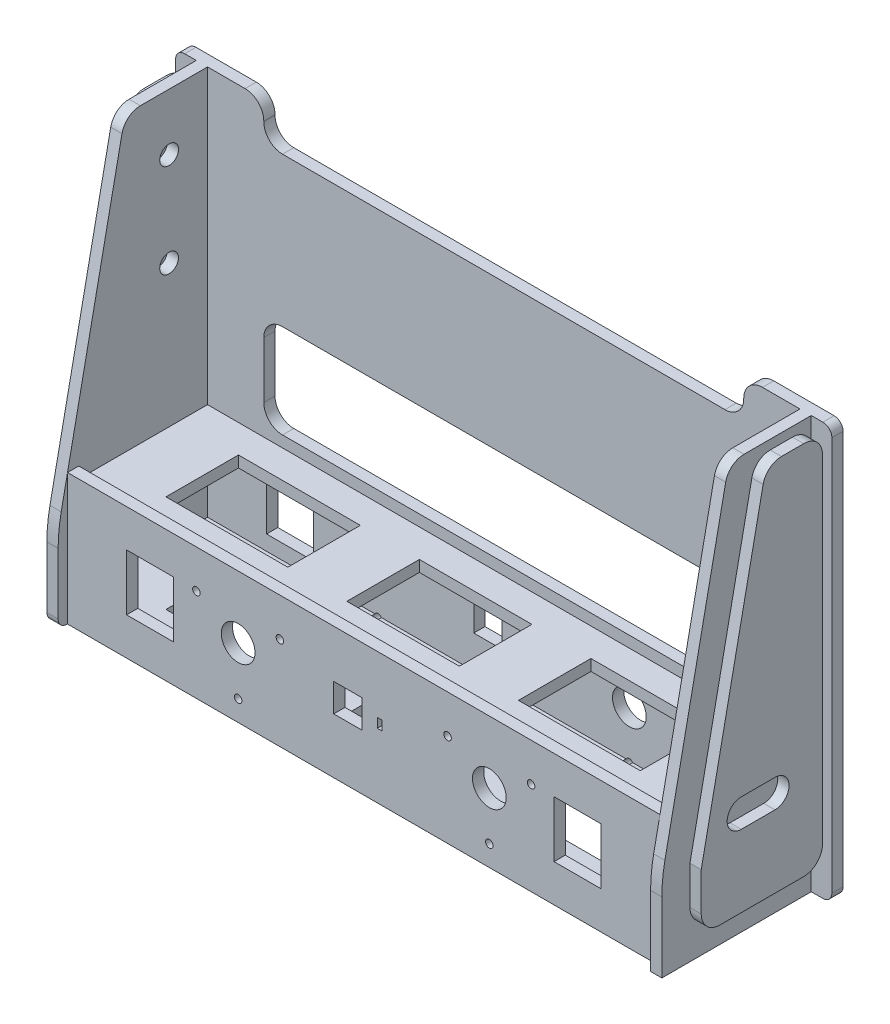
SolidWorks part; units mm, degrees
material "Birch plywood FK"
ref_plane "Спереди" through (0, 0, 0) normal (0, 0, 1) x (1, 0, 0)
ref_plane "Сверху" through (0, 0, 0) normal (0, 1, 0) x (1, 0, 0)
ref_plane "Справа" through (0, 0, 0) normal (1, 0, 0) x (0, 0, -1)
sketch "Эскиз1" plane through (0, 0, 0) normal (1, 0, 0) x (0, 0, -1)
  line L0 (0, 220) -> (0, 0)
  line L1 (0, 0) -> (-95, 0)
  line L2 (-95, 0) -> (-50, 220)
  line L3 (-50, 220) -> (0, 220)
  dimension "D1" = 220
  dimension "D2" = 95
  dimension "D3" = 50
extrude "Бобышка-Вытянуть1" add sketch "Эскиз1" along normal blind 340
sketch "Эскиз2" plane through (0, 220, 0) normal (0, 1, 0) x (1, 0, 0)
  line L0 (170, -95) -> (170, 0) construction
  line L1 (340, -95) -> (0, -95) construction
  line L2 (340, 0) -> (0, 0) construction
  line L3 (340, -50) -> (340, -95) construction
  line L4 (12, -95) -> (328, -95)
  line L5 (12, -95) -> (12, -6)
  line L6 (12, -6) -> (328, -6)
  line L7 (328, -95) -> (328, -6)
  line L8 (12, -95) -> (328, -6) construction
  line L9 (12, -6) -> (328, -95) construction
  point P6 (170, -50.5)
  dimension "D1" = 12
  dimension "D2" = 6
extrude "Вырез-Вытянуть1" cut sketch "Эскиз2" against normal offset from surface (150 mm away) 70 up to face at (170, 0, 47.5)
sketch "Эскиз3" plane through (0, 70, 0) normal (0, 1, 0) x (1, 0, 0)
  line L0 (340, -95) -> (0, -95) construction
  line L1 (12, -80.6818) -> (328, -80.6818)
  line L2 (12, -80.6818) -> (12, -95)
  line L3 (12, -95) -> (328, -95)
  line L4 (328, -80.6818) -> (328, -95)
extrude "Вырез-Вытянуть2" cut sketch "Эскиз3" against normal through all
sketch "Эскиз4" plane through (0, 0, 80.6818) normal (0, 0, 1) x (1, 0, 0)
  line L0 (170, 70) -> (170, 0) construction
  line L1 (12, 70) -> (328, 70) construction
  line L2 (328, 0) -> (12, 0) construction
  line L3 (12, 0) -> (12, 70) construction
  line L4 (328, 12) -> (12, 12)
  line L5 (328, 12) -> (328, 58)
  line L6 (328, 58) -> (12, 58)
  line L7 (12, 12) -> (12, 58)
  line L8 (328, 12) -> (12, 58) construction
  line L9 (328, 58) -> (12, 12) construction
  line L10 (12, 70) -> (328, 70) construction
  line L12 (328, 64) -> (12, 64)
  line L13 (328, 64) -> (328, 70)
  line L14 (328, 70) -> (12, 70)
  line L15 (12, 64) -> (12, 70)
  line L16 (328, 64) -> (12, 70) construction
  line L17 (328, 70) -> (12, 64) construction
  line L18 (328, 6) -> (12, 6)
  line L19 (328, 6) -> (328, 0)
  line L20 (328, 0) -> (12, 0)
  line L21 (12, 6) -> (12, 0)
  line L22 (328, 6) -> (12, 0) construction
  line L23 (328, 0) -> (12, 6) construction
  point P6 (170, 35)
  point P15 (170, 67)
  point P21 (170, 3)
  dimension "D1" = 12
  dimension "D2" = 6
extrude "Вырез-Вытянуть3" cut sketch "Эскиз4" against normal offset from surface (68.6818 mm away) 6 from offset 6 up to face at (170, 110, 0) offset against normal yes
sketch "Эскиз5" plane through (0, 0, 6) normal (0, 0, 1) x (1, 0, 0)
  line L0 (170, 220) -> (170, 70) construction
  line L1 (328, 220) -> (12, 220) construction
  line L2 (12, 70) -> (328, 70) construction
  line L3 (12, 64) -> (12, 220) construction
  line L4 (298, 70) -> (42, 70)
  line L5 (298, 70) -> (298, 120)
  line L6 (298, 120) -> (42, 120)
  line L7 (42, 70) -> (42, 120)
  line L8 (298, 70) -> (42, 120) construction
  line L9 (298, 120) -> (42, 70) construction
  point P6 (170, 95)
  dimension "D1" = 30
  dimension "D2" = 50
extrude "Вырез-Вытянуть4" cut sketch "Эскиз5" against normal through all
sketch "Эскиз6" plane through (0, 70, 0) normal (0, 1, 0) x (1, 0, 0)
  line L0 (170, 0) -> (170, -80.6818) construction
  line L1 (42, 0) -> (298, 0) construction
  line L2 (12, -80.6818) -> (328, -80.6818) construction
  line L3 (12, -6) -> (42, -6) construction
  line L4 (140, -40.3409) -> (12, -40.3409) construction
  line L5 (12, -6) -> (12, -74.6818) construction
  line L6 (200, -59.6818) -> (140, -59.6818)
  line L7 (200, -59.6818) -> (200, -21)
  line L8 (200, -21) -> (140, -21)
  line L9 (140, -59.6818) -> (140, -21)
  line L10 (200, -59.6818) -> (140, -21) construction
  line L11 (200, -21) -> (140, -59.6818) construction
  line L13 (108.5, -21) -> (43.5, -21)
  line L14 (328, -6) -> (328, -74.6818) construction
  line L15 (328, -40.3409) -> (200, -40.3409) construction
  line L16 (108.5, -21) -> (108.5, -59.6818)
  line L17 (108.5, -59.6818) -> (43.5, -59.6818)
  line L19 (43.5, -21) -> (43.5, -59.6818)
  line L20 (108.5, -21) -> (43.5, -59.6818) construction
  line L21 (108.5, -59.6818) -> (43.5, -21) construction
  line L22 (296.5, -21) -> (231.5, -21)
  line L23 (296.5, -21) -> (296.5, -59.6818)
  line L24 (296.5, -59.6818) -> (231.5, -59.6818)
  line L25 (231.5, -21) -> (231.5, -59.6818)
  line L26 (296.5, -21) -> (231.5, -59.6818) construction
  line L27 (296.5, -59.6818) -> (231.5, -21) construction
  point P6 (170, -40.3409)
  point P18 (76, -40.3409)
  point P28 (264, -40.3409)
  dimension "D1" = 15
  dimension "D2" = 60
  dimension "D3" = 65
extrude "Вырез-Вытянуть5" cut sketch "Эскиз6" against normal through all
sketch "Эскиз8" plane through (0, 0, 0) normal (-1, 0, 0) x (0, 0, 1)
  line L0 (95, 0) -> (0, 0) construction
  line L1 (85.6818, 70) -> (95, 70)
  line L2 (85.6818, 70) -> (85.6818, 0)
  line L3 (85.6818, 0) -> (95, 0)
  line L4 (95, 70) -> (95, 0)
  line L5 (80.6818, 0) -> (80.6818, 70) construction
  line L6 (80.6818, 70) -> (74.6818, 70) construction
  dimension "D1" = 5
extrude "Вырез-Вытянуть7" cut sketch "Эскиз8" against normal through all
sketch "Эскиз10" plane through (0, 220, 0) normal (0, 1, 0) x (1, 0, 0)
  line L0 (328, -6) -> (12, -6) construction
  line L1 (0, 0) -> (-5, 0)
  line L2 (0, 0) -> (0, -6)
  line L3 (0, -6) -> (-5, -6)
  line L4 (-5, 0) -> (-5, -6)
  line L5 (340, 0) -> (345, 0)
  line L6 (340, 0) -> (340, -6)
  line L7 (340, -6) -> (345, -6)
  line L8 (345, 0) -> (345, -6)
  dimension "D1" = 5
  dimension "D2" = 5
extrude "Бобышка-Вытянуть3" add sketch "Эскиз10" against normal up to surface (220 mm away) up to face at (170, 0, 63.0114)
sketch "Эскиз12" plane through (0, 0, 0) normal (-1, 0, 0) x (0, 0, 1)
  circle A0 centre (26.5, 189.7) radius 5
  circle A1 centre (26.5, 139.7) radius 5
  dimension "D1" = 10
extrude "Вырез-Вытянуть9" cut sketch "Эскиз12" against normal offset from surface (328 mm away) 6 from offset 6 up to face at (340, 75.1111, 50.2409) offset against normal yes
sketch "Эскиз13" plane through (0, 0, 6) normal (0, 0, 1) x (1, 0, 0)
  line L0 (334, 184.7) -> (345, 184.7) construction
  line L1 (345, 0) -> (345, 220) construction
  line L2 (306.85, 184.7) -> (306.85, 144.7) construction
  line L3 (334, 144.7) -> (345, 144.7) construction
  line L4 (306.85, 164.7) -> (345, 164.7) construction
  circle A0 centre (306.85, 164.7) radius 16.4
  circle A2 centre (291.35, 180.2) radius 1.5
  circle A3 centre (322.35, 180.2) radius 1.5
  circle A4 centre (322.35, 149.2) radius 1.5
  circle A5 centre (291.35, 149.2) radius 1.5
  circle A6 centre (306.85, 164.7) radius 16.4 construction
  point P0 (306.85, 164.7)
  dimension "D1" = 3
extrude "Вырез-Вытянуть10" cut sketch "Эскиз13" against normal through all
fillet "Скругление2" radius 10 2 edges at (6, 220, 50) (334, 220, 50)
fillet "Скругление4" radius 80 2 edges at (334, 45.5556, 85.6818) (6, 45.5556, 85.6818)
sketch "Эскиз16" plane through (0, 0, 80.6818) normal (0, 0, 1) x (1, 0, 0)
  circle A0 centre (103, 36.7238) radius 9
  circle A1 centre (237, 36.7238) radius 9
  dimension "D1" = 18
extrude "Вырез-Вытянуть12" cut sketch "Эскиз16" against normal through all
sketch "Эскиз19" plane through (0, 0, 80.6818) normal (0, 0, 1) x (1, 0, 0)
  line L0 (161.5, 37) -> (178.5, 37) construction
  line L1 (169, 29.5) -> (154, 29.5)
  line L2 (169, 29.5) -> (169, 44.5)
  line L3 (169, 44.5) -> (154, 44.5)
  line L4 (154, 29.5) -> (154, 44.5)
  line L5 (169, 29.5) -> (154, 44.5) construction
  line L6 (169, 44.5) -> (154, 29.5) construction
  line L7 (179.75, 34.5) -> (177.25, 34.5)
  line L8 (179.75, 34.5) -> (179.75, 39.5)
  line L9 (179.75, 39.5) -> (177.25, 39.5)
  line L10 (177.25, 34.5) -> (177.25, 39.5)
  line L11 (179.75, 34.5) -> (177.25, 39.5) construction
  line L12 (179.75, 39.5) -> (177.25, 34.5) construction
  line L13 (170, 37) -> (170, -29) construction
  line L14 (153.0926, -29) -> (186.9074, -29) construction
  line L15 (60, 24.5) -> (280, 24.5) construction
  circle A0 centre (125.2775, 49.5857) radius 2
  circle A1 centre (80.7225, 49.5857) radius 2
  circle A2 centre (103, 11) radius 2
  circle A3 centre (214.7225, 49.5857) radius 2
  circle A4 centre (259.2775, 49.5857) radius 2
  circle A5 centre (237, 11) radius 2
  point P0 (161.5, 37)
  point P5 (178.5, 37)
  dimension "D7" = 4
  dimension "D1" = 5
  dimension "D2" = 2.5
  dimension "D3" = 12.5
  dimension "D4" = 17
  dimension "D5" = 15
  dimension "D6" = 15
extrude "Вырез-Вытянуть15" cut sketch "Эскиз19" against normal through all
fillet "Скругление5" radius 4.8 5 edges at (-5, 220, 3) (6, 0, 85.6818) (-5, 0, 3) (345, 0, 3) (345, 220, 3)
fillet "Скругление6" radius 10 4 edges at (298, 70, 3) (298, 120, 3) (42, 70, 3) (42, 120, 3)
sketch "Эскиз20" plane through (0, 0, 6) normal (0, 0, 1) x (1, 0, 0)
  line L0 (319.5142, 124.6) -> (309.5142, 124.6) construction
  line L1 (319.5142, 124.1) -> (309.5142, 124.1)
  line L2 (319.5142, 125.1) -> (309.5142, 125.1)
  line L3 (319.5142, 115.1) -> (309.5142, 115.1) construction
  line L4 (319.5142, 114.6) -> (309.5142, 114.6)
  line L5 (319.5142, 115.6) -> (309.5142, 115.6)
  arc A0 (319.5142, 124.1) -> (319.5142, 125.1) centre (319.5142, 124.6) ccw
  arc A1 (309.5142, 125.1) -> (309.5142, 124.1) centre (309.5142, 124.6) ccw
  arc A2 (319.5142, 114.6) -> (319.5142, 115.6) centre (319.5142, 115.1) ccw
  arc A3 (309.5142, 115.6) -> (309.5142, 114.6) centre (309.5142, 115.1) ccw
  point P2 (314.5142, 124.6)
  point P7 (314.5142, 115.1)
  dimension "D1" = 1
  dimension "D2" = 10
extrude "Вырез-Вытянуть16" cut sketch "Эскиз20" against normal through all
sketch "Эскиз21" plane through (0, 0, 6) normal (0, 0, 1) x (1, 0, 0)
  line L0 (170, 220) -> (170, 0) construction
  line L1 (328, 220) -> (12, 220) construction
  line L2 (328, 0) -> (12, 0) construction
  line L3 (12, 70) -> (12, 212.004) construction
  line L4 (298, 199.7) -> (42, 199.7)
  line L5 (298, 199.7) -> (298, 220)
  line L6 (298, 220) -> (42, 220)
  line L7 (42, 199.7) -> (42, 220)
  line L8 (298, 199.7) -> (42, 220) construction
  line L9 (298, 220) -> (42, 199.7) construction
  line L10 (156.6778, 202.7) -> (190.4925, 202.7) construction
  point P6 (170, 209.85)
  dimension "D1" = 30
  dimension "D2" = 3
extrude "Вырез-Вытянуть17" cut sketch "Эскиз21" against normal through all
fillet "Скругление7" radius 10 4 edges at (298, 199.7, 3) (298, 220, 3) (42, 199.7, 3) (42, 220, 3)
ref_plane "Плоскость1" through (170, 0, 0) normal (-1, 0, 0) x (0, 0, 1)
sketch "Эскиз22" plane through (0, 0, 0) normal (-1, 0, 0) x (0, 0, 1)
  line L0 (16, 215) -> (27.8611, 215)
  line L2 (37.6583, 207.004) -> (70.6818, 45.5556)
  line L3 (70.6818, 45.5556) -> (70.6818, 25)
  line L4 (60.6818, 15) -> (16, 15)
  line L5 (6, 220) -> (41.8384, 220) construction
  line L6 (51.6356, 212.004) -> (84.059, 53.4893) construction
  line L7 (80.8818, 0) -> (6, 0) construction
  line L8 (85.6818, 37.4576) -> (85.6818, 4.8) construction
  line L9 (6, 0) -> (6, 220) construction
  line L10 (6, 205) -> (6, 220)
  line L11 (6, 220) -> (50, 220)
  line L12 (50, 220) -> (85.6818, 45.5556)
  line L13 (85.6818, 45.5556) -> (85.6818, 0)
  line L14 (85.6818, 0) -> (6, 0)
  line L15 (6, 0) -> (6, 25)
  line L16 (49.3409, 61) -> (31.3409, 61) construction
  line L17 (49.3409, 53.5) -> (31.3409, 53.5)
  line L18 (49.3409, 68.5) -> (31.3409, 68.5)
  line L19 (40.3409, 64) -> (40.3409, 58) construction
  line L20 (6, 64) -> (74.6818, 64) construction
  line L21 (6, 58) -> (74.6818, 58) construction
  arc A0 (70.6818, 25) -> (60.6818, 15) centre (60.6818, 25) cw
  arc A1 (27.8611, 215) -> (37.6583, 207.004) centre (27.8611, 205) cw
  arc A2 (16, 215) -> (6, 205) centre (16, 205) ccw
  arc A3 (6, 25) -> (16, 15) centre (16, 25) ccw
  arc A4 (49.3409, 53.5) -> (49.3409, 68.5) centre (49.3409, 61) ccw
  arc A5 (31.3409, 68.5) -> (31.3409, 53.5) centre (31.3409, 61) ccw
  point P34 (40.3409, 61)
  dimension "D1" = 10
  dimension "D5" = 20
  dimension "D2" = 5
  dimension "D3" = 15
  dimension "D4" = 15
  dimension "D6" = 15
  dimension "D7" = 18
extrude "Вырез-Вытянуть18" cut sketch "Эскиз22" against normal blind 6
mirror "Зеркальное отражение1" about plane through (170, 0, 0) normal (-1, 0, 0) of "Вырез-Вытянуть18"
sketch "Эскиз23" plane through (0, 0, 80.6818) normal (0, 0, 1) x (1, 0, 0)
  line L0 (170, 70) -> (170, 0) construction
  line L1 (12, 70) -> (328, 70) construction
  line L2 (328, 0) -> (12, 0) construction
  line L3 (271.5, 50) -> (296.5, 20) construction
  line L4 (12, 0) -> (12, 70) construction
  line L5 (12, 35) -> (170, 35) construction
  line L6 (170, 35) -> (328, 35) construction
  line L7 (328, 0) -> (328, 70) construction
  line L8 (68.5, 20) -> (43.5, 20)
  line L9 (68.5, 20) -> (68.5, 50)
  line L10 (68.5, 50) -> (43.5, 50)
  line L11 (43.5, 20) -> (43.5, 50)
  line L12 (68.5, 20) -> (43.5, 50) construction
  line L13 (68.5, 50) -> (43.5, 20) construction
  line L14 (271.5, 20) -> (296.5, 50) construction
  line L15 (296.5, 20) -> (296.5, 50)
  line L16 (271.5, 50) -> (296.5, 50)
  line L17 (271.5, 20) -> (271.5, 50)
  line L18 (271.5, 20) -> (296.5, 20)
  line L19 (43.5, 58) -> (43.5, 64) construction
  point P13 (56, 35)
  point P22 (284, 35)
  dimension "D1" = 30
  dimension "D2" = 25
extrude "Вырез-Вытянуть19" cut sketch "Эскиз23" against normal through all
